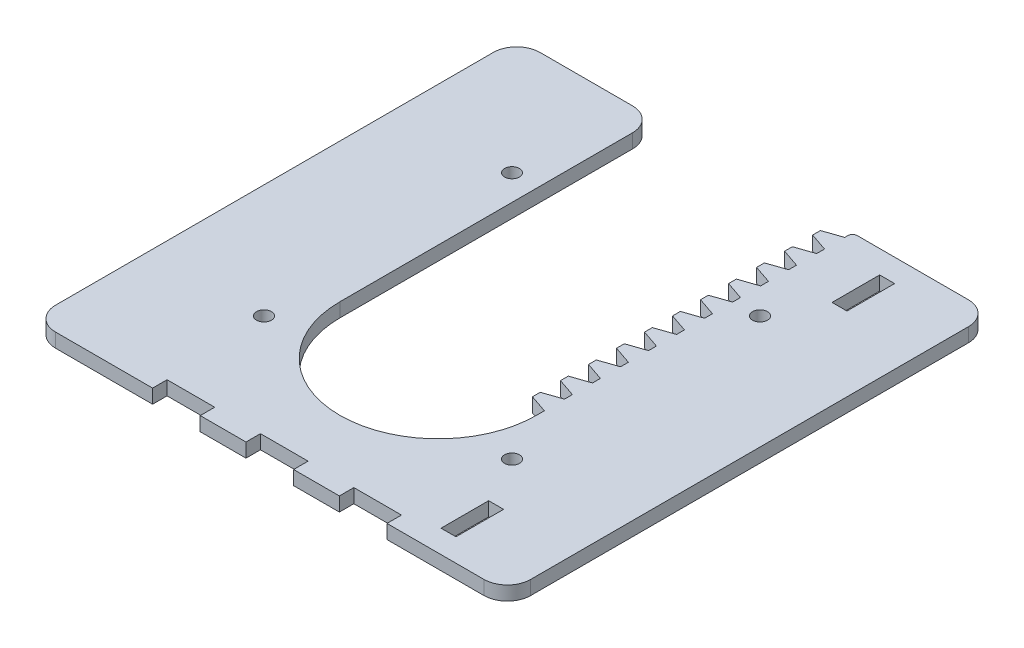
SolidWorks part; units mm, degrees
ref_plane "Front Plane" through (0, 0, 0) normal (0, 0, 1) x (1, 0, 0)
ref_plane "Top Plane" through (0, 0, 0) normal (0, 1, 0) x (1, 0, 0)
ref_plane "Right Plane" through (0, 0, 0) normal (1, 0, 0) x (0, 0, -1)
sketch "Sketch1" plane through (0, 0, 0) normal (0, 1, 0) x (1, 0, 0)
  line L0 (0, 0) -> (0, 21) construction
  line L1 (17.1887, 0) -> (0, 0) construction
  line L2 (21.0585, 3.843) -> (17.1887, 5.1665) construction
  line L3 (17.1887, 5.1665) -> (17.1887, 6.8335) construction
  line L4 (17.1887, 6.8335) -> (21.0585, 8.157) construction
  line L5 (21.0585, 9.843) -> (21.0585, 8.157) construction
  line L6 (21.0585, 9.843) -> (17.1887, 11.1665) construction
  line L7 (17.1887, 11.1665) -> (17.1887, 12.8335) construction
  line L8 (17.1887, 12.8335) -> (21.0585, 14.157) construction
  line L9 (21.0585, 15.843) -> (21.0585, 14.157) construction
  line L10 (21.0585, 15.843) -> (17.1887, 17.1665) construction
  line L11 (17.1887, 17.1665) -> (17.1887, 18.8335) construction
  line L12 (17.1887, 18.8335) -> (21.0585, 20.157) construction
  line L13 (21.0585, 21.843) -> (21.0585, 20.157) construction
  line L14 (21.0585, 21.843) -> (17.1887, 23.1665) construction
  line L15 (17.1887, 23.1665) -> (17.1887, 24.8335) construction
  line L16 (17.1887, 24.8335) -> (21.0585, 26.157) construction
  line L17 (21.0585, 27.843) -> (21.0585, 26.157) construction
  line L18 (21.0585, 27.843) -> (17.1887, 29.1665) construction
  line L19 (17.1887, 29.1665) -> (17.1887, 30.8335) construction
  line L20 (17.1887, 30.8335) -> (21.0585, 32.157) construction
  line L21 (21.0585, 33.843) -> (21.0585, 32.157) construction
  line L22 (21.0585, 33.843) -> (17.1887, 35.1665) construction
  line L23 (17.1887, 35.1665) -> (17.1887, 36.8335) construction
  line L24 (17.1887, 36.8335) -> (21.0585, 38.157) construction
  line L25 (21.0585, 39.843) -> (21.0585, 38.157) construction
  line L26 (21.0585, 39.843) -> (17.1887, 41.1665) construction
  line L27 (17.1887, 41.1665) -> (17.1887, 42.8335) construction
  line L28 (17.1887, 42.8335) -> (21.0585, 44.157) construction
  line L29 (21.0585, 45.843) -> (21.0585, 44.157) construction
  line L30 (21.0585, 45.843) -> (17.1887, 47.1665) construction
  line L31 (17.1887, 47.1665) -> (17.1887, 48.8335) construction
  line L32 (17.1887, 48.8335) -> (21.0585, 50.157) construction
  line L33 (21.0585, 51.843) -> (21.0585, 50.157) construction
  line L34 (21.0585, 51.843) -> (17.1887, 53.1665) construction
  line L35 (17.1887, 53.1665) -> (17.1887, 54.8335) construction
  line L36 (17.1887, 54.8335) -> (21.0585, 56.157) construction
  line L37 (21.0585, 57.843) -> (21.0585, 56.157) construction
  line L38 (21.0585, 57.843) -> (17.1887, 59.1665) construction
  line L39 (17.1887, 59.1665) -> (17.1887, 60.8335) construction
  line L40 (17.1887, 60.8335) -> (21.0585, 62.157) construction
  line L41 (21.0585, 62.157) -> (21.0585, 62.843) construction
  line L42 (45.8722, 63.843) -> (22.0585, 63.843) construction
  line L43 (50.8722, -34.9014) -> (50.8722, 58.843) construction
  line L44 (45.8722, -39.9014) -> (-45.8722, -39.9014) construction
  line L45 (-50.8722, 58.843) -> (-50.8722, -34.9014) construction
  line L46 (-45.8722, 63.843) -> (-22.0585, 63.843) construction
  line L47 (-21.0585, -3.843) -> (-21.0585, 62.843) construction
  line L48 (21.0585, -2.157) -> (21.0585, -3.843) construction
  line L49 (21.0585, -2.157) -> (17.1887, -0.8335) construction
  line L50 (17.1887, -0.8335) -> (17.1887, 0.8335) construction
  line L51 (17.1887, 0.8335) -> (21.0585, 2.157) construction
  line L52 (21.0585, 3.843) -> (21.0585, 2.157) construction
  line L53 (21.0585, 3.843) -> (17.1887, 5.1665)
  line L54 (17.1887, 5.1665) -> (17.1887, 6.8335)
  line L55 (17.1887, 6.8335) -> (21.0585, 8.157)
  line L56 (21.0585, 9.843) -> (21.0585, 8.157)
  line L57 (21.0585, 9.843) -> (17.1887, 11.1665)
  line L58 (17.1887, 11.1665) -> (17.1887, 12.8335)
  line L59 (17.1887, 12.8335) -> (21.0585, 14.157)
  line L60 (21.0585, 15.843) -> (21.0585, 14.157)
  line L61 (21.0585, 15.843) -> (17.1887, 17.1665)
  line L62 (17.1887, 17.1665) -> (17.1887, 18.8335)
  line L63 (17.1887, 18.8335) -> (21.0585, 20.157)
  line L64 (21.0585, 21.843) -> (21.0585, 20.157)
  line L65 (21.0585, 21.843) -> (17.1887, 23.1665)
  line L66 (17.1887, 23.1665) -> (17.1887, 24.8335)
  line L67 (17.1887, 24.8335) -> (21.0585, 26.157)
  line L68 (21.0585, 27.843) -> (21.0585, 26.157)
  line L69 (21.0585, 27.843) -> (17.1887, 29.1665)
  line L70 (17.1887, 29.1665) -> (17.1887, 30.8335)
  line L71 (17.1887, 30.8335) -> (21.0585, 32.157)
  line L72 (21.0585, 33.843) -> (21.0585, 32.157)
  line L73 (21.0585, 33.843) -> (17.1887, 35.1665)
  line L74 (17.1887, 35.1665) -> (17.1887, 36.8335)
  line L75 (17.1887, 36.8335) -> (21.0585, 38.157)
  line L76 (21.0585, 39.843) -> (21.0585, 38.157)
  line L77 (21.0585, 39.843) -> (17.1887, 41.1665)
  line L78 (17.1887, 41.1665) -> (17.1887, 42.8335)
  line L79 (17.1887, 42.8335) -> (21.0585, 44.157)
  line L80 (21.0585, 45.843) -> (21.0585, 44.157)
  line L81 (21.0585, 45.843) -> (17.1887, 47.1665)
  line L82 (17.1887, 47.1665) -> (17.1887, 48.8335)
  line L83 (17.1887, 48.8335) -> (21.0585, 50.157)
  line L84 (21.0585, 51.843) -> (21.0585, 50.157)
  line L85 (21.0585, 51.843) -> (17.1887, 53.1665)
  line L86 (17.1887, 53.1665) -> (17.1887, 54.8335)
  line L87 (17.1887, 54.8335) -> (21.0585, 56.157)
  line L88 (21.0585, 57.843) -> (21.0585, 56.157)
  line L89 (21.0585, 57.843) -> (17.1887, 59.1665)
  line L90 (17.1887, 59.1665) -> (17.1887, 60.8335)
  line L91 (17.1887, 60.8335) -> (21.0585, 62.157)
  line L92 (21.0585, 62.157) -> (21.0585, 62.843)
  line L93 (45.8722, 63.843) -> (22.0585, 63.843)
  line L94 (50.8722, -34.9014) -> (50.8722, 58.843)
  line L95 (45.8722, -39.9014) -> (-45.8722, -39.9014)
  line L96 (-50.8722, 58.843) -> (-50.8722, -34.9014)
  line L97 (-45.8722, 63.843) -> (-26.0585, 63.843)
  line L98 (-21.0585, -3.843) -> (-21.0585, 58.843)
  line L99 (21.0585, -2.157) -> (21.0585, -3.843)
  line L100 (21.0585, -2.157) -> (17.1887, -0.8335)
  line L101 (17.1887, -0.8335) -> (17.1887, 0.8335)
  line L102 (17.1887, 0.8335) -> (21.0585, 2.157)
  line L103 (21.0585, 3.843) -> (21.0585, 2.157)
  line L104 (0, 63.843) -> (0, -39.9014) construction
  line L105 (-51.8722, 11.9708) -> (51.8722, 11.9708) construction
  line L106 (0, 11.9708) -> (-51.8722, -39.9014) construction
  line L107 (51.8722, -24.9014) -> (-51.8722, -24.9014) construction
  line L108 (-36.8722, -39.9014) -> (-36.8722, 63.843) construction
  line L109 (36.8722, -39.9014) -> (36.8722, 63.843) construction
  line L110 (45.8722, -39.9014) -> (51.8722, -39.9014) construction
  line L111 (51.8722, -39.9014) -> (51.8722, 63.843) construction
  line L112 (51.8722, 63.843) -> (-51.8722, 63.843) construction
  line L113 (17.1887, 60) -> (0, 60) construction
  line L114 (-51.8722, 63.843) -> (-51.8722, -39.9014) construction
  line L115 (-51.8722, -39.9014) -> (-45.8722, -39.9014) construction
  circle A0 centre (0, 0) radius 21 construction
  circle A1 centre (0, 60) radius 21 construction
  arc A2 (22.0585, 63.843) -> (21.0585, 62.843) centre (22.0585, 62.843) ccw construction
  arc A3 (50.8722, 58.843) -> (45.8722, 63.843) centre (45.8722, 58.843) ccw construction
  arc A4 (45.8722, -39.9014) -> (50.8722, -34.9014) centre (45.8722, -34.9014) ccw construction
  arc A5 (-50.8722, -34.9014) -> (-45.8722, -39.9014) centre (-45.8722, -34.9014) ccw construction
  arc A6 (-45.8722, 63.843) -> (-50.8722, 58.843) centre (-45.8722, 58.843) ccw construction
  arc A8 (-21.0585, -3.843) -> (21.0585, -3.843) centre (0, -3.843) ccw construction
  arc A9 (22.0585, 63.843) -> (21.0585, 62.843) centre (22.0585, 62.843) ccw
  arc A10 (50.8722, 58.843) -> (45.8722, 63.843) centre (45.8722, 58.843) ccw
  arc A11 (45.8722, -39.9014) -> (50.8722, -34.9014) centre (45.8722, -34.9014) ccw
  arc A12 (-50.8722, -34.9014) -> (-45.8722, -39.9014) centre (-45.8722, -34.9014) ccw
  arc A13 (-45.8722, 63.843) -> (-50.8722, 58.843) centre (-45.8722, 58.843) ccw
  arc A14 (-21.0585, 58.843) -> (-26.0585, 63.843) centre (-26.0585, 58.843) ccw
  arc A15 (-21.0585, -3.843) -> (21.0585, -3.843) centre (0, -3.843) ccw
  circle A16 centre (26.5585, -14.5877) radius 1.6 construction
  circle A17 centre (-26.5585, -14.5877) radius 1.6 construction
  circle A18 centre (-26.5585, 38.5292) radius 1.6 construction
  circle A19 centre (26.5585, 38.5292) radius 1.6 construction
  circle A20 centre (26.5585, -14.5877) radius 1.6
  circle A21 centre (-26.5585, -14.5877) radius 1.6
  circle A22 centre (-26.5585, 38.5292) radius 1.6
  circle A23 centre (26.5585, 38.5292) radius 1.6
  circle A24 centre (0, 60) radius 21 construction
sketch "Sketch2" plane through (0, 0, 0) normal (0, 0, 1) x (1, 0, 0)
  line L0 (0, 0) -> (0, 3) construction
  line L1 (-50.8722, 0) -> (50.8722, 0)
  line L2 (-50.8722, 0) -> (-50.8722, 3)
  line L3 (-50.8722, 3) -> (50.8722, 3)
  line L4 (50.8722, 0) -> (50.8722, 3)
  line L5 (-50.8722, 3) -> (-51.8722, 3) construction
  line L6 (-51.8722, 3) -> (-51.8722, 3.75) construction
  line L7 (-51.8722, 3.75) -> (51.8722, 3.75) construction
  line L8 (51.8722, 3.75) -> (51.8722, 3) construction
  line L9 (51.8722, 3) -> (50.8722, 3) construction
  line L10 (50.8722, 0) -> (51.8722, 0) construction
  line L11 (51.8722, 0) -> (51.8722, -0.75) construction
  line L12 (51.8722, -0.75) -> (-51.8722, -0.75) construction
  line L13 (-51.8722, -0.75) -> (-51.8722, 0) construction
  line L14 (-51.8722, 0) -> (-50.8722, 0) construction
  line L15 (59.7, 47.7) -> (59.7, 44.7) construction
  dimension "D2" = 0.75
extrude "Boss-Extrude1" add sketch "Sketch1" along normal up to vertex (3 mm away) up to point (-50.8722, 3, 0)
ref_plane "edge" through (0, 0, -63.843) normal (0, 0, 1) x (1, 0, 0)
sketch "Sketch4" plane through (0, 0, 0) normal (0, 1, 0) x (1, 0, 0)
  line L12 (-25.0418, -23.0877) -> (-25.0418, -20.0877) construction
  line L13 (-15.0251, -23.0877) -> (-15.0251, -20.0877) construction
  line L14 (-5.0084, -23.0877) -> (-5.0084, -20.0877) construction
  line L15 (5.0084, -23.0877) -> (5.0084, -20.0877) construction
  line L16 (15.0251, -23.0877) -> (15.0251, -20.0877) construction
  line L17 (25.0418, -20.0877) -> (25.0418, -23.0877) construction
  line L18 (32.0585, -20.0877) -> (35.0585, -20.0877) construction
  line L30 (-25.0418, -23.0877) -> (-25.0418, -20.0877)
  line L31 (-15.0251, -23.0877) -> (-15.0251, -20.0877)
  line L32 (-5.0084, -23.0877) -> (-5.0084, -20.0877)
  line L33 (5.0084, -23.0877) -> (5.0084, -20.0877)
  line L34 (15.0251, -23.0877) -> (15.0251, -20.0877)
  line L35 (25.0418, -20.0877) -> (25.0418, -23.0877)
  line L36 (-35.0585, 47.0292) -> (35.0585, 47.0292) construction
  line L37 (-32.0585, 44.0292) -> (32.0585, 44.0292) construction
  line L38 (-32.0585, -20.0877) -> (-32.0585, 44.0292) construction
  line L39 (-35.0585, -23.0877) -> (-35.0585, 47.0292) construction
  line L40 (-32.0585, -20.0877) -> (32.0585, -20.0877) construction
  line L41 (-35.0585, -23.0877) -> (35.0585, -23.0877) construction
  line L42 (32.0585, -20.0877) -> (32.0585, 44.0292) construction
  line L43 (35.0585, -23.0877) -> (35.0585, 47.0292) construction
  line L44 (-35.0585, 47.0292) -> (35.0585, 47.0292)
  line L45 (-32.0585, 44.0292) -> (32.0585, 44.0292)
  line L46 (-32.0585, -20.0877) -> (-32.0585, 44.0292)
  line L47 (-35.0585, -23.0877) -> (-35.0585, 47.0292)
  line L48 (-32.0585, -20.0877) -> (32.0585, -20.0877)
  line L49 (-35.0585, -23.0877) -> (35.0585, -23.0877)
  line L50 (32.0585, -20.0877) -> (32.0585, 44.0292)
  line L51 (35.0585, -23.0877) -> (35.0585, 47.0292)
  line L52 (-23.0585, 44.0292) -> (-23.0585, 47.0292) construction
  line L53 (-23.0585, 44.0292) -> (-23.0585, 47.0292)
  line L54 (23.0585, 44.0292) -> (23.0585, 47.0292) construction
  line L55 (23.0585, 44.0292) -> (23.0585, 47.0292)
  line L56 (-32.0585, 44.0292) -> (-35.0585, 44.0292) construction
  line L57 (-25.0418, 47.0292) -> (-25.0418, 44.0292) construction
  line L58 (25.0418, 47.0292) -> (25.0418, 44.0292) construction
  line L59 (32.0585, 47.0292) -> (32.0585, 44.0292) construction
  line L66 (-32.0585, -20.0877) -> (-32.0585, -23.0877) construction
sketch "Sketch3" plane through (0, 0, 0) normal (0, 1, 0) x (1, 0, 0)
  line L0 (32.0585, 37.0125) -> (35.0585, 37.0125) construction
  line L1 (25.0418, 47.0292) -> (25.0418, 44.0292) construction
  line L2 (25.0418, 44.0292) -> (32.0585, 44.0292) construction
  line L3 (32.0585, 44.0292) -> (32.0585, 37.0125) construction
  line L4 (32.0585, 37.0125) -> (35.0585, 37.0125) construction
  line L5 (35.0585, 37.0125) -> (35.0585, 47.0292) construction
  line L6 (35.0585, 47.0292) -> (25.0418, 47.0292) construction
  line L7 (35.0585, -23.0877) -> (35.0585, 47.0292) construction
  line L8 (32.0585, 11.9708) -> (0, 11.9708) construction
  line L9 (0, 11.9708) -> (0, 44.0292) construction
  line L10 (32.0585, 11.9708) -> (0, 11.9708) construction
  line L11 (0, 11.9708) -> (0, 44.0292) construction
  line L13 (35.0585, 26.9958) -> (32.0585, 26.9958) construction
  line L14 (35.0585, 16.9791) -> (32.0585, 16.9791) construction
  line L15 (32.0585, -20.0877) -> (32.0585, 44.0292) construction
  line L16 (35.0585, 26.9958) -> (32.0585, 26.9958) construction
  line L17 (35.0585, 26.9958) -> (35.0585, 16.9791) construction
  line L18 (35.0585, 16.9791) -> (32.0585, 16.9791) construction
  line L19 (32.0585, 26.9958) -> (32.0585, 16.9791) construction
  line L20 (35.1585, 27.0958) -> (35.1585, 16.8791)
  line L21 (35.1585, 16.8791) -> (31.9585, 16.8791)
  line L22 (31.9585, 27.0958) -> (31.9585, 16.8791)
  line L23 (35.1585, 27.0958) -> (31.9585, 27.0958)
  line L24 (35.1585, 36.9125) -> (35.1585, 47.1292)
  line L25 (35.1585, 47.1292) -> (24.9418, 47.1292)
  line L26 (24.9418, 47.1292) -> (24.9418, 43.9292)
  line L27 (24.9418, 43.9292) -> (31.9585, 43.9292)
  line L28 (31.9585, 43.9292) -> (31.9585, 36.9125)
  line L29 (31.9585, 36.9125) -> (35.1585, 36.9125)
  line L30 (35.1585, -3.1543) -> (31.9585, -3.1543)
  line L31 (31.9585, -3.1543) -> (31.9585, 7.0624)
  line L32 (35.1585, 7.0624) -> (31.9585, 7.0624)
  line L33 (35.1585, -3.1543) -> (35.1585, 7.0624)
  line L34 (31.9585, -19.9877) -> (31.9585, -12.971)
  line L35 (24.9418, -19.9877) -> (31.9585, -19.9877)
  line L36 (24.9418, -23.1877) -> (24.9418, -19.9877)
  line L37 (35.1585, -23.1877) -> (24.9418, -23.1877)
  line L38 (35.1585, -12.971) -> (35.1585, -23.1877)
  line L39 (31.9585, -12.971) -> (35.1585, -12.971)
  line L40 (-31.9585, 43.9292) -> (-31.9585, 36.9125)
  line L41 (-24.9418, 43.9292) -> (-31.9585, 43.9292)
  line L42 (-24.9418, 47.1292) -> (-24.9418, 43.9292)
  line L43 (-35.1585, 47.1292) -> (-24.9418, 47.1292)
  line L44 (-35.1585, 36.9125) -> (-35.1585, 47.1292)
  line L45 (-31.9585, 36.9125) -> (-35.1585, 36.9125)
  line L46 (-35.1585, 27.0958) -> (-35.1585, 16.8791)
  line L47 (-35.1585, 16.8791) -> (-31.9585, 16.8791)
  line L48 (-31.9585, 27.0958) -> (-31.9585, 16.8791)
  line L49 (-35.1585, 27.0958) -> (-31.9585, 27.0958)
  line L50 (-35.1585, -3.1543) -> (-31.9585, -3.1543)
  line L51 (-31.9585, -3.1543) -> (-31.9585, 7.0624)
  line L52 (-35.1585, 7.0624) -> (-31.9585, 7.0624)
  line L53 (-35.1585, -3.1543) -> (-35.1585, 7.0624)
  line L54 (-35.1585, -12.971) -> (-35.1585, -23.1877)
  line L55 (-31.9585, -12.971) -> (-35.1585, -12.971)
  line L56 (-31.9585, -19.9877) -> (-31.9585, -12.971)
  line L57 (-24.9418, -19.9877) -> (-31.9585, -19.9877)
  line L58 (-24.9418, -23.1877) -> (-24.9418, -19.9877)
  line L59 (-35.1585, -23.1877) -> (-24.9418, -23.1877)
  dimension "D1" = 0.1
extrude "Cut-Extrude1" [suppressed] cut sketch "Sketch3" along normal through all
sketch "Sketch6" plane through (0, 0, 0) normal (0, 1, 0) x (1, 0, 0)
  line L0 (31.7722, 58.943) -> (34.9722, 58.943)
  line L1 (31.8722, 58.843) -> (34.8722, 58.843) construction
  line L2 (31.8722, 58.843) -> (31.8722, 48.843) construction
  line L3 (31.8722, 48.843) -> (34.8722, 48.843) construction
  line L4 (34.8722, 58.843) -> (34.8722, 48.843) construction
  line L5 (31.8722, -24.9014) -> (34.8722, -24.9014) construction
  line L6 (31.8722, -24.9014) -> (31.8722, -34.9014) construction
  line L7 (31.8722, -34.9014) -> (34.8722, -34.9014) construction
  line L8 (34.8722, -24.9014) -> (34.8722, -34.9014) construction
  line L9 (25, -36.9014) -> (15, -36.9014) construction
  line L10 (25, -36.9014) -> (25, -39.9014) construction
  line L11 (25, -39.9014) -> (15, -39.9014) construction
  line L12 (15, -36.9014) -> (15, -39.9014) construction
  line L13 (5, -36.9014) -> (-5, -36.9014) construction
  line L14 (5, -36.9014) -> (5, -39.9014) construction
  line L15 (5, -39.9014) -> (-5, -39.9014) construction
  line L16 (-5, -36.9014) -> (-5, -39.9014) construction
  line L17 (-15, -36.9014) -> (-25, -36.9014) construction
  line L18 (-15, -36.9014) -> (-15, -39.9014) construction
  line L19 (-15, -39.9014) -> (-25, -39.9014) construction
  line L20 (-25, -36.9014) -> (-25, -39.9014) construction
  line L21 (34.9722, 58.943) -> (34.9722, 48.743)
  line L22 (31.7722, 48.743) -> (34.9722, 48.743)
  line L23 (31.7722, 58.943) -> (31.7722, 48.743)
  line L24 (31.7722, -24.8014) -> (34.9722, -24.8014)
  line L25 (34.9722, -24.8014) -> (34.9722, -35.0014)
  line L26 (31.7722, -35.0014) -> (34.9722, -35.0014)
  line L27 (31.7722, -24.8014) -> (31.7722, -35.0014)
  line L28 (25.1, -36.8014) -> (14.9, -36.8014)
  line L29 (14.9, -36.8014) -> (14.9, -40.0014)
  line L30 (25.1, -40.0014) -> (14.9, -40.0014)
  line L31 (25.1, -36.8014) -> (25.1, -40.0014)
  line L32 (5.1, -36.8014) -> (-5.1, -36.8014)
  line L33 (-5.1, -36.8014) -> (-5.1, -40.0014)
  line L34 (5.1, -40.0014) -> (-5.1, -40.0014)
  line L35 (5.1, -36.8014) -> (5.1, -40.0014)
  line L36 (-14.9, -36.8014) -> (-25.1, -36.8014)
  line L37 (-25.1, -36.8014) -> (-25.1, -40.0014)
  line L38 (-14.9, -40.0014) -> (-25.1, -40.0014)
  line L39 (-14.9, -36.8014) -> (-14.9, -40.0014)
  dimension "D1" = 0.1
extrude "Cut-Extrude4" cut sketch "Sketch6" along normal through all
